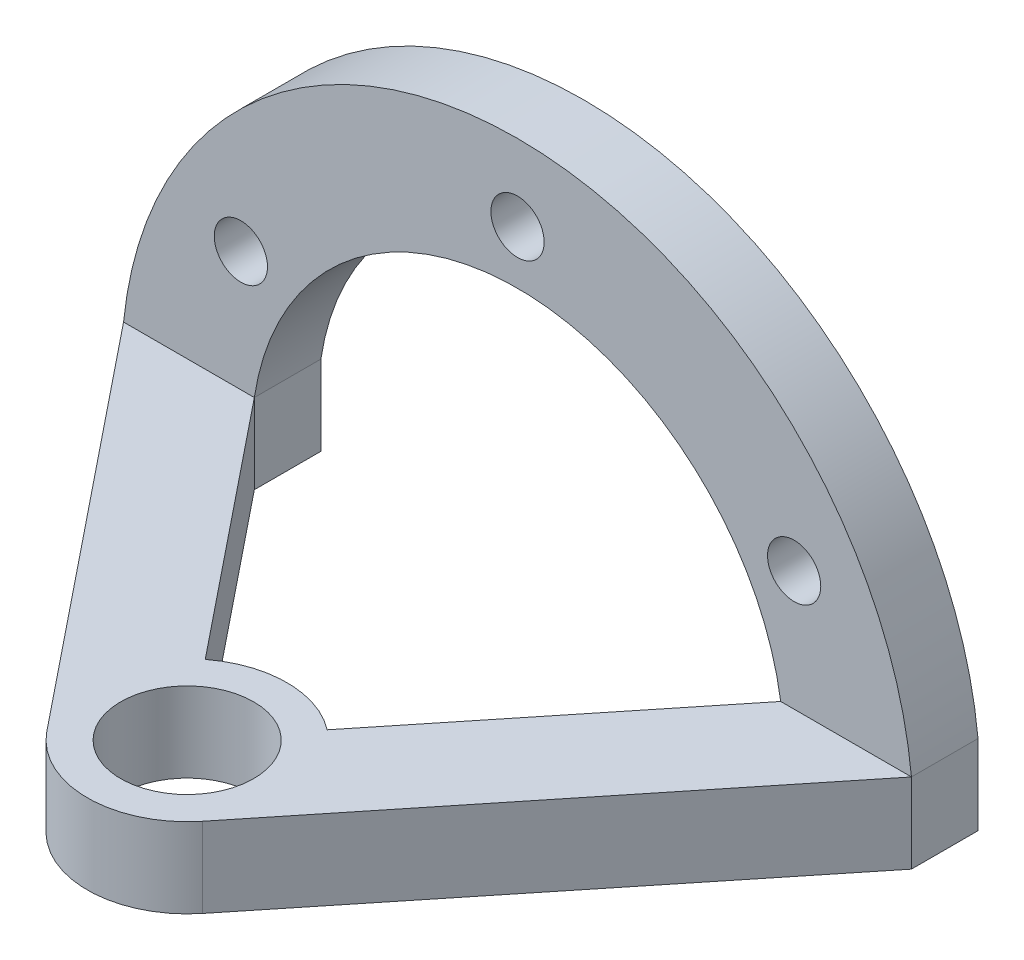
SolidWorks part; units mm, degrees
ref_plane "Front Plane" through (0, 0, 0) normal (0, 0, 1) x (1, 0, 0)
ref_plane "Top Plane" through (0, 0, 0) normal (0, 1, 0) x (1, 0, 0)
ref_plane "Right Plane" through (0, 0, 0) normal (1, 0, 0) x (0, 0, -1)
sketch "Sketch1" plane through (0, 0, 0) normal (0, 0, 1) x (1, 0, 0)
  line L0 (0, 0) -> (0, 24) construction
  line L1 (-29.5984, 3) -> (-19.7737, 3)
  line L2 (19.7737, 3) -> (29.5984, 3)
  circle A3 centre (0, 24) radius 2
  arc A7 (19.7737, 3) -> (-19.7737, 3) centre (0, 0) ccw
  circle A14 centre (0, 0) radius 24 construction
  circle A15 centre (20.7846, 12) radius 2
  circle A19 centre (-20.7846, 12) radius 2
  arc A20 (29.5984, 3) -> (-29.5984, 3) centre (0, 0) ccw
  circle A21 centre (-20.7846, -12) radius 2 [skipped]
  circle A22 centre (0, -24) radius 2 [skipped]
  circle A23 centre (20.7846, -12) radius 2 [skipped]
  point P0 (26.4469, -13.6877)
  point P16 (0, 0)
  dimension "D1" = 48
  dimension "D2" = 40
  dimension "D3" = 4
  dimension "D5" = 59.5
  dimension "D4" = 6
  dimension "D6" = 3
extrude "Boss-Extrude1" add sketch "Sketch1" along normal blind 5
sketch "Sketch2" plane through (0, 3, 0) normal (0, -1, 0) x (1, 0, 0)
  line L0 (19.7737, 0) -> (29.5984, 0) construction
  line L1 (29.5984, 0) -> (29.5984, 5) construction
  line L3 (19.7737, 5) -> (19.7737, 0) construction
  line L4 (-29.5984, 0) -> (-19.7737, 0) construction
  line L5 (-19.7737, 0) -> (-19.7737, 5) construction
  line L7 (-29.5984, 5) -> (-29.5984, 0) construction
  line L8 (19.7737, 0) -> (29.5984, 0)
  line L9 (29.5984, 0) -> (29.5984, 5)
  line L11 (19.7737, 5) -> (19.7737, 0)
  line L12 (-29.5984, 0) -> (-19.7737, 0)
  line L13 (-19.7737, 0) -> (-19.7737, 5)
  line L15 (-29.5984, 5) -> (-29.5984, 0)
  line L16 (0, 0) -> (0, 29.82) construction
  line L17 (-29.5984, 5) -> (-5.8432, 34.5218)
  line L18 (-19.7737, 5) -> (-4.5806, 23.8813)
  line L19 (5.8432, 34.5218) -> (29.5984, 5)
  line L20 (-29.5984, 5) -> (-19.7737, 5) construction
  line L21 (4.5806, 23.8813) -> (19.7737, 5)
  circle A0 centre (0, 29.82) radius 5
  arc A1 (-4.5806, 23.8813) -> (4.5806, 23.8813) centre (0, 29.82) ccw
  arc A2 (5.8432, 34.5218) -> (-5.8432, 34.5218) centre (0, 29.82) ccw
  dimension "D1" = 10
  dimension "D2" = 15
  dimension "D3" = 24.82
extrude "Boss-Extrude2" add sketch "Sketch2" along normal blind 6
